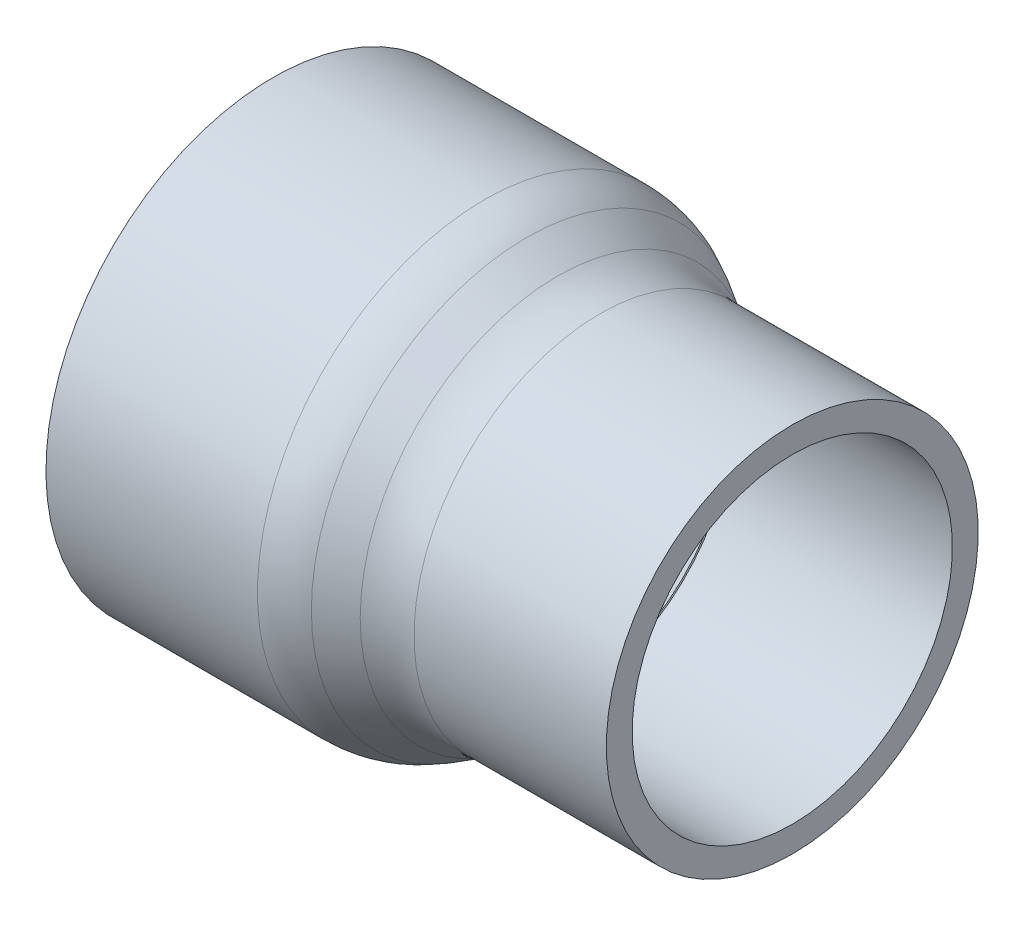
SolidWorks part; units mm, degrees
ref_plane "Front Plane" through (0, 0, 0) normal (0, 0, 1) x (1, 0, 0)
ref_plane "Top Plane" through (0, 0, 0) normal (0, 1, 0) x (1, 0, 0)
ref_plane "Right Plane" through (0, 0, 0) normal (1, 0, 0) x (0, 0, -1)
sketch "Sketch0" plane through (0, 0, 0) normal (0, 0, 1) x (1, 0, 0)
  line L0 (-39.37, 0) -> (6.096, 0) construction
  line L2 (-4.572, 0) -> (6.096, 0) construction
  line L3 (-39.37, 0) -> (39.37, 0) construction
  line L4 (-39.37, 34.417) -> (-39.37, -34.417) construction
  line L5 (-4.572, 30.0863) -> (-39.37, 30.3149) construction
  line L6 (-4.572, 30.0863) -> (-4.572, -30.0863) construction
  line L7 (-4.572, -30.0863) -> (-39.37, -30.3149) construction
  line L8 (-39.37, 30.3149) -> (-39.37, -30.3149) construction
  line L9 (39.37, 24.2824) -> (39.37, -24.2824) construction
  line L10 (39.37, 28.194) -> (39.37, -28.194) construction
  line L11 (6.096, 20.447) -> (6.096, -20.447) construction
  line L12 (6.096, 24.0538) -> (6.096, -24.0538) construction
  line L13 (6.096, -24.0538) -> (39.37, -24.2824) construction
  line L14 (-4.572, 26.2509) -> (-4.572, -26.2509) construction
  line L15 (6.096, 24.0538) -> (39.37, 24.2824) construction
  dimension "N" = 10.668
  dimension "M" = 68.834
  dimension "OD A" = 60.6298
  dimension "OD B" = 60.1726
  dimension "ID" = 52.5018
  dimension "L" = 78.74
  dimension "ID2" = 40.894
  dimension "OD B2" = 48.1076
  dimension "OD A2" = 48.5648
  dimension "M2" = 56.388
  dimension "C" = 34.798
  dimension "C2" = 33.274
sketch "Sketch1" plane through (0, 0, 0) normal (0, 0, 1) x (1, 0, 0)
  line L0 (-39.37, 0) -> (6.096, 0) construction
  line L1 (-39.37, 0) -> (6.096, 0) construction
  line L2 (-4.572, -30.0863) -> (5.9998, -23.8897)
  line L3 (0, -32.1613) -> (-2.0743, -28.6223) construction
  line L4 (-39.37, -34.417) -> (-39.37, -30.3149)
  line L5 (-39.37, -30.3149) -> (-4.572, -30.0863)
  line L7 (5.9998, -23.8897) -> (6.096, -24.0538)
  line L8 (-3.8484, -34.417) -> (6.7685, -28.194)
  line L9 (-3.8484, -34.417) -> (-39.37, -34.417)
  line L10 (0, 0) -> (0, -32.1613) construction
  line L12 (6.096, -24.0538) -> (39.37, -24.2824)
  line L13 (39.37, -24.2824) -> (39.37, -28.194)
  line L14 (39.37, -28.194) -> (6.7685, -28.194)
  line L15 (6.096, -20.447) -> (6.096, -24.0538) construction
  dimension "D1" = 30
revolve "Revolve1" add sketch "Sketch1" angle 360 about L1
fillet "Fillet1" radius 12.7 2 edges at (-3.8484, -34.417, 0) (6.7685, -28.194, 0)
other "CPoint1" parameters "Diameter"=38.1, "StubLength"=114.3
ref_axis "Axis1" through (16.096, 0, 0) along (-1, 0, 0)
other "CPoint2" parameters "Diameter"=50.8, "StubLength"=57.15
ref_axis "Axis2" through (-14.572, 0, 0) along (1, 0, 0)
other "RPoint1"
